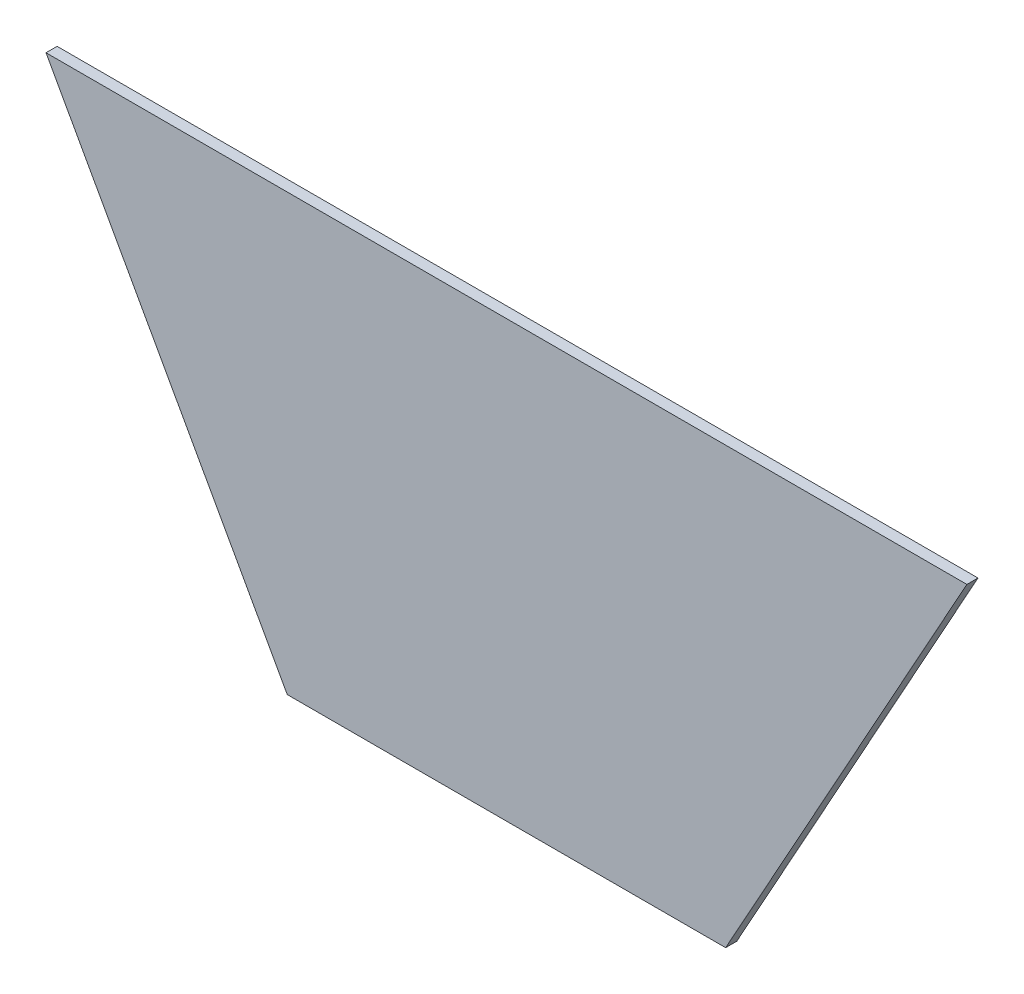
SolidWorks part; units mm, degrees
material "Pine"
ref_plane "Front Plane" through (0, 0, 0) normal (0, 0, 1) x (1, 0, 0)
ref_plane "Top Plane" through (0, 0, 0) normal (0, 1, 0) x (1, 0, 0)
ref_plane "Right Plane" through (0, 0, 0) normal (1, 0, 0) x (0, 0, -1)
sketch "Sketch1" plane through (0, 0, 0) normal (0, 0, 1) x (1, 0, 0)
  line L0 (396.886, 13.4872) -> (476.928, 157.8869)
  line L1 (-73.014, 13.4872) -> (396.886, 13.4872)
  line L5 (-73.014, 13.4872) -> (-153.0561, 157.8869)
  line L6 (-331.6115, 480.0093) -> (655.4834, 480.0093)
  line L7 (161.936, 13.4872) -> (161.936, 516.6792) construction
  line L8 (575.4413, 335.6096) -> (508.7953, 372.5521)
  line L9 (508.7953, 372.5521) -> (410.282, 194.8294)
  line L11 (459.5387, 283.6907) -> (579.3504, 217.278) construction
  line L12 (575.4413, 335.6096) -> (655.4834, 480.0093)
  line L13 (476.928, 157.8869) -> (410.282, 194.8294)
  line L14 (-251.5694, 335.6096) -> (-184.9234, 372.5521)
  line L15 (-184.9234, 372.5521) -> (-86.4101, 194.8294)
  line L16 (-153.0561, 157.8869) -> (-86.4101, 194.8294)
  line L17 (-251.5694, 335.6096) -> (-331.6115, 480.0093)
  line L18 (575.4413, 335.6096) -> (476.928, 157.8869)
  line L19 (-251.5694, 335.6096) -> (-153.0561, 157.8869)
  dimension "D1" = 469.9
  dimension "D2" = 533.4
  dimension "D3" = 266.7
  dimension "D4" = 533.4
  dimension "D5" = 119
  dimension "D6" = 987.0949
  dimension "D7" = 203.2
  dimension "D8" = 76.2
  dimension "D9" = 76.2
  dimension "D10" = 119
extrude "Boss-Extrude1" add sketch "Sketch1" along normal blind 11.9062 contours L17 L14 L15 L16 L5 L1 L0 L13 L9 L8 L12 L6 | L18 L8 L9 L13 | L14 L19 L16 L15 region at (161.936, 275.264, 0) region at (492.8617, 265.2195, 0) region at (-168.9898, 265.2195, 0)
sketch "Sketch2" plane through (0, 0, 11.9062) normal (0, 0, 1) x (1, 0, 0)
  line L0 (575.4413, 335.6096) -> (476.928, 157.8869)
  line L1 (476.928, 157.8869) -> (410.282, 194.8294)
  line L2 (410.282, 194.8294) -> (508.7953, 372.5521)
  line L3 (508.7953, 372.5521) -> (575.4413, 335.6096)
  line L4 (-251.5694, 335.6096) -> (-184.9234, 372.5521)
  line L5 (-184.9234, 372.5521) -> (-86.4101, 194.8294)
  line L6 (-86.4101, 194.8294) -> (-153.0561, 157.8869)
  line L7 (-153.0561, 157.8869) -> (-251.5694, 335.6096)
extrude "Cut-Extrude1" [suppressed] cut sketch "Sketch2" against normal through all
